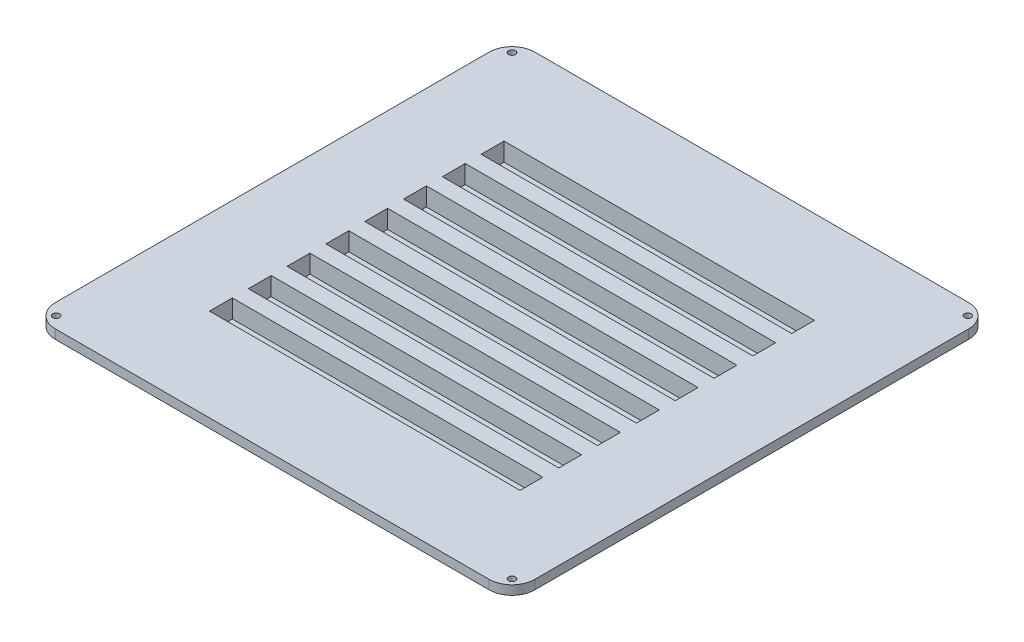
SolidWorks part; units mm, degrees
ref_plane "Front Plane" through (0, 0, 0) normal (0, 0, 1) x (1, 0, 0)
ref_plane "Top Plane" through (0, 0, 0) normal (0, 1, 0) x (1, 0, 0)
ref_plane "Right Plane" through (0, 0, 0) normal (1, 0, 0) x (0, 0, -1)
sketch "Sketch1" plane through (0, 0, 0) normal (0, 1, 0) x (1, 0, 0)
  line L0 (-101, -101) -> (-101, 101)
  line L5 (-105, -105) -> (105, -105)
  line L6 (-105, -105) -> (-105, 105)
  line L7 (-105, 105) -> (105, 105)
  line L8 (105, -105) -> (105, 105)
  line L9 (-101, 101) -> (101, 101)
  line L10 (101, -101) -> (101, 101)
  line L11 (-101, -101) -> (101, -101)
  line L12 (-101, 101) -> (-99.8333, 99.8333) construction
  line L13 (-55, 0) -> (55, 0) construction
  line L14 (-101, -101) -> (-99.8333, -99.8333) construction
  line L15 (0, -55) -> (0, 55) construction
  line L16 (101, -101) -> (99.8333, -99.8333) construction
  line L17 (101, 101) -> (99.8333, 99.8333) construction
  circle A1 centre (-99.8333, 99.8333) radius 1.5
  circle A2 centre (-99.8333, -99.8333) radius 1.5
  circle A3 centre (99.8333, -99.8333) radius 1.5
  circle A4 centre (99.8333, 99.8333) radius 1.5
  point P0 (0, 0)
  point P6 (-105, 0)
  point P7 (0, 105)
  dimension "D3" = 4
  dimension "D4" = 3
  dimension "D1" = 210
  dimension "D2" = 210
  dimension "D5" = 1.65
  dimension "D6" = 45
extrude "MainExtrude" add sketch "Sketch1" along normal blind 4 contours L6 L5 L8 L7
extrude "ScrewHoles" cut sketch "Sketch1<6>" along normal up to surface (4 mm away) contours A1 | A2 | A3 | A4 up to face at (0, 4, 0)
sketch "Sketch1<6>" plane through (0, 0, 0) normal (0, 1, 0) x (1, 0, 0) same geometry as "Sketch1"
fillet "RoundedCorners" radius 10 4 edges at (-105, 2, -105) (-105, 2, 105) (105, 2, -105) (105, 2, 105)
sketch "Sketch3" plane through (0, 0, 0) normal (0, 1, 0) x (1, 0, 0)
  line L145 (-68, 76.5) -> (68, 76.5) construction
  line L146 (-68, 76.5) -> (-68, -76.5) construction
  line L147 (-68, -76.5) -> (68, -76.5) construction
  line L148 (68, 76.5) -> (68, -76.5) construction
  line L149 (-68, 76.5) -> (68, -76.5) construction
  line L151 (68, 76.5) -> (-68, -76.5) construction
  line L152 (-68, 59.5) -> (68, 59.5) construction
  line L154 (-68, 42.5) -> (68, 42.5) construction
  line L155 (-68, 25.5) -> (68, 25.5) construction
  line L157 (-68, 8.5) -> (68, 8.5) construction
  line L158 (-68, -8.5) -> (68, -8.5) construction
  line L159 (-68, -25.5) -> (68, -25.5) construction
  line L160 (-68, -42.5) -> (68, -42.5) construction
  line L161 (-68, -59.5) -> (68, -59.5) construction
  line L162 (-68, 54.5) -> (68, 54.5)
  line L163 (-68, 37.5) -> (68, 37.5)
  line L164 (-68, 20.5) -> (68, 20.5)
  line L165 (-68, 3.5) -> (68, 3.5)
  line L166 (-68, -13.5) -> (68, -13.5)
  line L167 (-68, -30.5) -> (68, -30.5)
  line L168 (-68, -47.5) -> (68, -47.5)
  line L169 (-68, -64.5) -> (68, -64.5)
  line L170 (-68, 64.5) -> (68, 64.5)
  line L171 (-68, 47.5) -> (68, 47.5)
  line L172 (-68, 30.5) -> (68, 30.5)
  line L173 (-68, 13.5) -> (68, 13.5)
  line L174 (-68, -3.5) -> (68, -3.5)
  line L175 (-68, -20.5) -> (68, -20.5)
  line L176 (-68, -37.5) -> (68, -37.5)
  line L177 (-68, -54.5) -> (68, -54.5)
  line L178 (-68, 54.5) -> (-68, 64.5)
  line L179 (68, 54.5) -> (68, 64.5)
  line L180 (-68, 37.5) -> (-68, 47.5)
  line L181 (68, 37.5) -> (68, 47.5)
  line L182 (-68, 20.5) -> (-68, 30.5)
  line L183 (68, 20.5) -> (68, 30.5)
  line L184 (-68, 3.5) -> (-68, 13.5)
  line L185 (68, 3.5) -> (68, 13.5)
  line L186 (-68, -13.5) -> (-68, -3.5)
  line L187 (68, -13.5) -> (68, -3.5)
  line L188 (-68, -30.5) -> (-68, -20.5)
  line L189 (68, -30.5) -> (68, -20.5)
  line L190 (-68, -47.5) -> (-68, -37.5)
  line L191 (68, -47.5) -> (68, -37.5)
  line L192 (-68, -64.5) -> (-68, -54.5)
  line L193 (68, -64.5) -> (68, -54.5)
  point P4 (0, 0)
  dimension "D1" = 136
  dimension "D2" = 153
  dimension "D3" = 17
  dimension "D4" = 17
  dimension "D5" = 17
  dimension "D6" = 17
  dimension "D7" = 17
  dimension "D8" = 17
  dimension "D9" = 17
  dimension "D11" = 17
  dimension "D13" = 5
  dimension "D14" = 129
  dimension "D10" = 17
  dimension "D12" = 5
extrude "Trench" cut sketch "Sketch3" along normal blind 10
sketch "Sketch4" plane through (0, 0, 0) normal (0, 1, 0) x (1, 0, 0)
  line L0 (68, -54.5) -> (68, -64.5) construction
  line L1 (68, -64.5) -> (-68, -64.5) construction
  line L2 (-68, -64.5) -> (-68, -54.5) construction
  line L3 (-68, -54.5) -> (68, -54.5) construction
  line L4 (68, -37.5) -> (68, -47.5) construction
  line L5 (68, -47.5) -> (-68, -47.5) construction
  line L6 (-68, -47.5) -> (-68, -37.5) construction
  line L7 (-68, -37.5) -> (68, -37.5) construction
  line L8 (68, -20.5) -> (68, -30.5) construction
  line L9 (68, -30.5) -> (-68, -30.5) construction
  line L10 (-68, -30.5) -> (-68, -20.5) construction
  line L11 (-68, -20.5) -> (68, -20.5) construction
  line L12 (68, -3.5) -> (68, -13.5) construction
  line L13 (68, -13.5) -> (-68, -13.5) construction
  line L14 (-68, -13.5) -> (-68, -3.5) construction
  line L15 (-68, -3.5) -> (68, -3.5) construction
  line L16 (68, 13.5) -> (68, 3.5) construction
  line L17 (68, 3.5) -> (-68, 3.5) construction
  line L18 (-68, 3.5) -> (-68, 13.5) construction
  line L19 (-68, 13.5) -> (68, 13.5) construction
  line L20 (68, 30.5) -> (68, 20.5) construction
  line L21 (68, 20.5) -> (-68, 20.5) construction
  line L22 (-68, 20.5) -> (-68, 30.5) construction
  line L23 (-68, 30.5) -> (68, 30.5) construction
  line L24 (68, 47.5) -> (68, 37.5) construction
  line L25 (68, 37.5) -> (-68, 37.5) construction
  line L26 (-68, 37.5) -> (-68, 47.5) construction
  line L27 (-68, 47.5) -> (68, 47.5) construction
  line L28 (68, 64.5) -> (68, 54.5) construction
  line L29 (68, 54.5) -> (-68, 54.5) construction
  line L30 (-68, 54.5) -> (-68, 64.5) construction
  line L31 (-68, 64.5) -> (68, 64.5) construction
  line L32 (68, -54.5) -> (68, -64.5)
  line L33 (68, -64.5) -> (-68, -64.5)
  line L34 (-68, -64.5) -> (-68, -54.5)
  line L35 (-68, -54.5) -> (68, -54.5)
  line L36 (68, -37.5) -> (68, -47.5)
  line L37 (68, -47.5) -> (-68, -47.5)
  line L38 (-68, -47.5) -> (-68, -37.5)
  line L39 (-68, -37.5) -> (68, -37.5)
  line L40 (68, -20.5) -> (68, -30.5)
  line L41 (68, -30.5) -> (-68, -30.5)
  line L42 (-68, -30.5) -> (-68, -20.5)
  line L43 (-68, -20.5) -> (68, -20.5)
  line L44 (68, -3.5) -> (68, -13.5)
  line L45 (68, -13.5) -> (-68, -13.5)
  line L46 (-68, -13.5) -> (-68, -3.5)
  line L47 (-68, -3.5) -> (68, -3.5)
  line L48 (68, 13.5) -> (68, 3.5)
  line L49 (68, 3.5) -> (-68, 3.5)
  line L50 (-68, 3.5) -> (-68, 13.5)
  line L51 (-68, 13.5) -> (68, 13.5)
  line L52 (68, 30.5) -> (68, 20.5)
  line L53 (68, 20.5) -> (-68, 20.5)
  line L54 (-68, 20.5) -> (-68, 30.5)
  line L55 (-68, 30.5) -> (68, 30.5)
  line L56 (68, 47.5) -> (68, 37.5)
  line L57 (68, 37.5) -> (-68, 37.5)
  line L58 (-68, 37.5) -> (-68, 47.5)
  line L59 (-68, 47.5) -> (68, 47.5)
  line L60 (68, 64.5) -> (68, 54.5)
  line L61 (68, 54.5) -> (-68, 54.5)
  line L62 (-68, 54.5) -> (-68, 64.5)
  line L63 (-68, 64.5) -> (68, 64.5)
  line L64 (70, 66.5) -> (70, 52.5)
  line L65 (70, 52.5) -> (-70, 52.5)
  line L66 (-70, 52.5) -> (-70, 66.5)
  line L67 (-70, 66.5) -> (70, 66.5)
  line L68 (70, 49.5) -> (70, 35.5)
  line L69 (70, 35.5) -> (-70, 35.5)
  line L70 (-70, 35.5) -> (-70, 49.5)
  line L71 (-70, 49.5) -> (70, 49.5)
  line L72 (70, 32.5) -> (70, 18.5)
  line L73 (70, 18.5) -> (-70, 18.5)
  line L74 (-70, 18.5) -> (-70, 32.5)
  line L75 (-70, 32.5) -> (70, 32.5)
  line L76 (70, 15.5) -> (70, 1.5)
  line L77 (70, 1.5) -> (-70, 1.5)
  line L78 (-70, 1.5) -> (-70, 15.5)
  line L79 (-70, 15.5) -> (70, 15.5)
  line L80 (70, -1.5) -> (70, -15.5)
  line L81 (70, -15.5) -> (-70, -15.5)
  line L82 (-70, -15.5) -> (-70, -1.5)
  line L83 (-70, -1.5) -> (70, -1.5)
  line L84 (70, -18.5) -> (70, -32.5)
  line L85 (70, -32.5) -> (-70, -32.5)
  line L86 (-70, -32.5) -> (-70, -18.5)
  line L87 (-70, -18.5) -> (70, -18.5)
  line L88 (70, -35.5) -> (70, -49.5)
  line L89 (70, -49.5) -> (-70, -49.5)
  line L90 (-70, -49.5) -> (-70, -35.5)
  line L91 (-70, -35.5) -> (70, -35.5)
  line L92 (70, -52.5) -> (70, -66.5)
  line L93 (70, -66.5) -> (-70, -66.5)
  line L94 (-70, -66.5) -> (-70, -52.5)
  line L95 (-70, -52.5) -> (70, -52.5)
  dimension "D1" = 2
extrude "Trench Walls" add sketch "Sketch4" against normal blind 4
sketch "Sketch5" plane through (0, -4, 0) normal (0, -1, 0) x (1, 0, 0)
  line L0 (-70, -66.5) -> (70, -66.5) construction
  line L1 (70, -66.5) -> (70, -52.5) construction
  line L2 (70, -52.5) -> (-70, -52.5) construction
  line L3 (-70, -52.5) -> (-70, -66.5) construction
  line L4 (-70, -49.5) -> (70, -49.5) construction
  line L5 (70, -49.5) -> (70, -35.5) construction
  line L6 (70, -35.5) -> (-70, -35.5) construction
  line L7 (-70, -35.5) -> (-70, -49.5) construction
  line L8 (-70, -32.5) -> (70, -32.5) construction
  line L9 (70, -32.5) -> (70, -18.5) construction
  line L10 (70, -18.5) -> (-70, -18.5) construction
  line L11 (-70, -18.5) -> (-70, -32.5) construction
  line L12 (-70, -15.5) -> (70, -15.5) construction
  line L13 (70, -15.5) -> (70, -1.5) construction
  line L14 (70, -1.5) -> (-70, -1.5) construction
  line L15 (-70, -1.5) -> (-70, -15.5) construction
  line L16 (-70, 1.5) -> (70, 1.5) construction
  line L17 (70, 1.5) -> (70, 15.5) construction
  line L18 (70, 15.5) -> (-70, 15.5) construction
  line L19 (-70, 15.5) -> (-70, 1.5) construction
  line L20 (-70, 18.5) -> (70, 18.5) construction
  line L21 (70, 18.5) -> (70, 32.5) construction
  line L22 (70, 32.5) -> (-70, 32.5) construction
  line L23 (-70, 32.5) -> (-70, 18.5) construction
  line L24 (-70, 35.5) -> (70, 35.5) construction
  line L25 (70, 35.5) -> (70, 49.5) construction
  line L26 (70, 49.5) -> (-70, 49.5) construction
  line L27 (-70, 49.5) -> (-70, 35.5) construction
  line L28 (-70, 52.5) -> (70, 52.5) construction
  line L29 (70, 52.5) -> (70, 66.5) construction
  line L30 (70, 66.5) -> (-70, 66.5) construction
  line L31 (-70, 66.5) -> (-70, 52.5) construction
  line L32 (-70, -66.5) -> (70, -66.5)
  line L33 (70, -66.5) -> (70, -52.5)
  line L34 (70, -52.5) -> (-70, -52.5)
  line L35 (-70, -52.5) -> (-70, -66.5)
  line L36 (-70, -49.5) -> (70, -49.5)
  line L37 (70, -49.5) -> (70, -35.5)
  line L38 (70, -35.5) -> (-70, -35.5)
  line L39 (-70, -35.5) -> (-70, -49.5)
  line L40 (-70, -32.5) -> (70, -32.5)
  line L41 (70, -32.5) -> (70, -18.5)
  line L42 (70, -18.5) -> (-70, -18.5)
  line L43 (-70, -18.5) -> (-70, -32.5)
  line L44 (-70, -15.5) -> (70, -15.5)
  line L45 (70, -15.5) -> (70, -1.5)
  line L46 (70, -1.5) -> (-70, -1.5)
  line L47 (-70, -1.5) -> (-70, -15.5)
  line L48 (-70, 1.5) -> (70, 1.5)
  line L49 (70, 1.5) -> (70, 15.5)
  line L50 (70, 15.5) -> (-70, 15.5)
  line L51 (-70, 15.5) -> (-70, 1.5)
  line L52 (-70, 18.5) -> (70, 18.5)
  line L53 (70, 18.5) -> (70, 32.5)
  line L54 (70, 32.5) -> (-70, 32.5)
  line L55 (-70, 32.5) -> (-70, 18.5)
  line L56 (-70, 35.5) -> (70, 35.5)
  line L57 (70, 35.5) -> (70, 49.5)
  line L58 (70, 49.5) -> (-70, 49.5)
  line L59 (-70, 49.5) -> (-70, 35.5)
  line L60 (-70, 52.5) -> (70, 52.5)
  line L61 (70, 52.5) -> (70, 66.5)
  line L62 (70, 66.5) -> (-70, 66.5)
  line L63 (-70, 66.5) -> (-70, 52.5)
extrude "Trench Bottom" add sketch "Sketch5" along normal blind 2
equation "\"1_LED\"= 17mm"
equation "\"2_LED\"= \"1_LED\" * 2"
equation "\"3_LED\"= \"1_LED\" * 3"
equation "\"4_LED\"= \"1_LED\" * 4"
equation "\"5_LED\"= \"1_LED\" * 5"
equation "\"6_LED\"= \"1_LED\" * 6"
equation "\"7_LED\"= \"1_LED\" * 7"
equation "\"8_LED\"= \"1_LED\" * 8"
equation "\"9_LED\"= \"1_LED\" * 9"
equation "\"10_LED\"= \"1_LED\" * 10"
equation "\"11_LED\"= \"1_LED\" * 11"
equation "\"12_LED\"= \"1_LED\" * 12"
